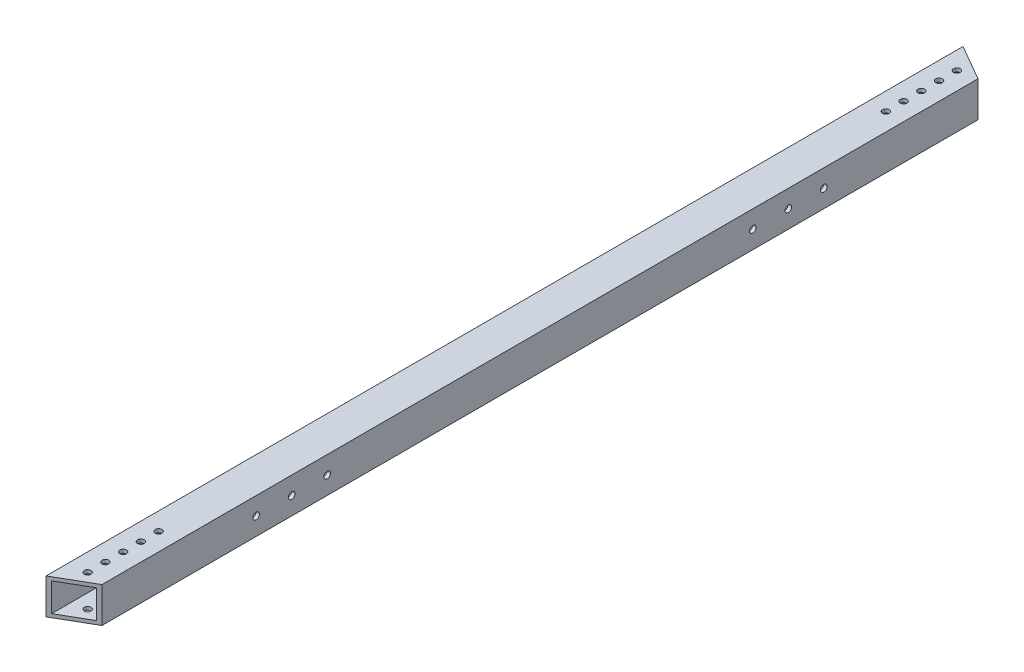
SolidWorks part; units mm, degrees
ref_plane "Front Plane" through (0, 0, 0) normal (0, 0, 1) x (1, 0, 0)
ref_plane "Top Plane" through (0, 0, 0) normal (0, 1, 0) x (1, 0, 0)
ref_plane "Right Plane" through (0, 0, 0) normal (1, 0, 0) x (0, 0, -1)
sketch "Sketch1" plane through (0, 0, 0) normal (0, 0, 1) x (1, 0, 0)
  line L0 (-10.16, 10.16) -> (10.16, 10.16)
  line L1 (-12.7, -12.7) -> (12.7, -12.7)
  line L2 (-12.7, -12.7) -> (-12.7, 12.7)
  line L3 (-12.7, 12.7) -> (12.7, 12.7)
  line L4 (12.7, -12.7) -> (12.7, 12.7)
  line L5 (-12.7, -12.7) -> (12.7, 12.7) construction
  line L6 (-12.7, 12.7) -> (12.7, -12.7) construction
  line L7 (10.16, -10.16) -> (10.16, 10.16)
  line L8 (-10.16, -10.16) -> (10.16, -10.16)
  line L9 (-10.16, -10.16) -> (-10.16, 10.16)
  point P0 (0, 0)
  dimension "D1" = 25.4
  dimension "D2" = 25.4
  dimension "D3" = 2.54
extrude "Boss-Extrude2" add sketch "Sketch1" along normal blind 656.5743
sketch "Sketch2" plane through (0, 12.7, 0) normal (0, 1, 0) x (1, 0, 0)
  line L0 (-12.7, -656.5743) -> (12.7, -641.9096)
  line L1 (12.7, -656.5743) -> (12.7, 0) construction
  line L2 (12.7, -641.9096) -> (12.7, -656.5743)
  line L3 (12.7, -656.5743) -> (-12.7, -656.5743)
  line L4 (-12.7, -328.2872) -> (12.7, -328.2872) construction
  line L5 (-12.7, -656.5743) -> (-12.7, 0) construction
  line L6 (12.7, 0) -> (-12.7, 0)
  line L7 (12.7, -14.6647) -> (12.7, 0)
  line L8 (-12.7, 0) -> (12.7, -14.6647)
  dimension "D1" = 30
extrude "Cut-Extrude1" cut sketch "Sketch2" against normal through all
sketch "Sketch3" plane through (0, 12.7, 0) normal (0, 1, 0) x (1, 0, 0)
  line L0 (0, -7.3323) -> (0, -649.242) construction
  line L1 (-12.7, 0) -> (12.7, -14.6647) construction
  line L2 (12.7, -641.9096) -> (-12.7, -656.5743) construction
  line L3 (12.7, -328.2872) -> (-12.7, -328.2872) construction
  line L4 (12.7, -641.9096) -> (12.7, -14.6647) construction
  line L5 (-12.7, -656.5743) -> (-12.7, 0) construction
  circle A5 centre (0, -639.4372) radius 2.3813
  circle A6 centre (0, -626.7372) radius 2.3813
  circle A7 centre (0, -614.0372) radius 2.3813
  circle A8 centre (0, -601.3372) radius 2.3813
  circle A9 centre (0, -588.6372) radius 2.3813
  circle A10 centre (0, -67.9372) radius 2.3812
  circle A11 centre (0, -55.2372) radius 2.3812
  circle A12 centre (0, -42.5372) radius 2.3812
  circle A13 centre (0, -29.8372) radius 2.3813
  circle A14 centre (0, -17.1372) radius 2.3813
  dimension "D3" = 4.7625
  dimension "D5" = 5
extrude "Cut-Extrude2" cut sketch "Sketch3" against normal through all
sketch "Sketch4" plane through (-12.7, 0, 0) normal (-1, 0, 0) x (0, 0, 1)
  line L0 (0, 0) -> (656.5743, 0) construction
  line L1 (656.5743, 12.7) -> (656.5743, -12.7) construction
  line L2 (328.2872, 12.7) -> (328.2872, -12.7) construction
  line L3 (656.5743, 12.7) -> (0, 12.7) construction
  line L4 (656.5743, -12.7) -> (0, -12.7) construction
  circle A0 centre (175.8872, 0) radius 2.3813
  circle A1 centre (150.4872, 0) radius 2.3813
  circle A2 centre (125.0872, 0) radius 2.3813
  circle A3 centre (531.4872, 0) radius 2.3812
  circle A4 centre (506.0872, 0) radius 2.3813
  circle A5 centre (480.6872, 0) radius 2.3812
  dimension "D1" = 4.7625
  dimension "D2" = 152.4
  dimension "D3" = 3
extrude "Cut-Extrude3" cut sketch "Sketch4" against normal through all
sketch "Sketch5" plane through (0, 12.7, 0) normal (0, 1, 0) x (1, 0, 0)
  line L0 (-12.7, -203.2) -> (12.7, -203.2) construction
  line L1 (-12.7, -656.5743) -> (-12.7, 0) construction
  line L2 (12.7, -641.9096) -> (12.7, -14.6647) construction
  line L4 (-12.7, -203.2) -> (12.7, -203.2)
  line L5 (-12.7, -203.2) -> (-12.7, -661.6049)
  line L6 (-12.7, -661.6049) -> (12.7, -661.6049)
  line L7 (12.7, -203.2) -> (12.7, -661.6049)
  dimension "D1" = 203.2
extrude "Cut-Extrude4" [suppressed] cut sketch "Sketch5" against normal through all
sketch "Sketch6" [suppressed] plane through (-12.7, 0, 0) normal (-1, 0, 0) x (0, 0, 1)
  line L0 (203.2, 12.7) -> (190.5, 12.7)
  line L1 (203.2, 12.7) -> (0, 12.7) construction
  line L2 (190.5, 12.7) -> (203.2, -12.7)
  line L3 (203.2, -12.7) -> (203.2, 12.7)
  dimension "D1" = 12.7
extrude "Cut-Extrude5" [suppressed] cut sketch "Sketch6" against normal through all
